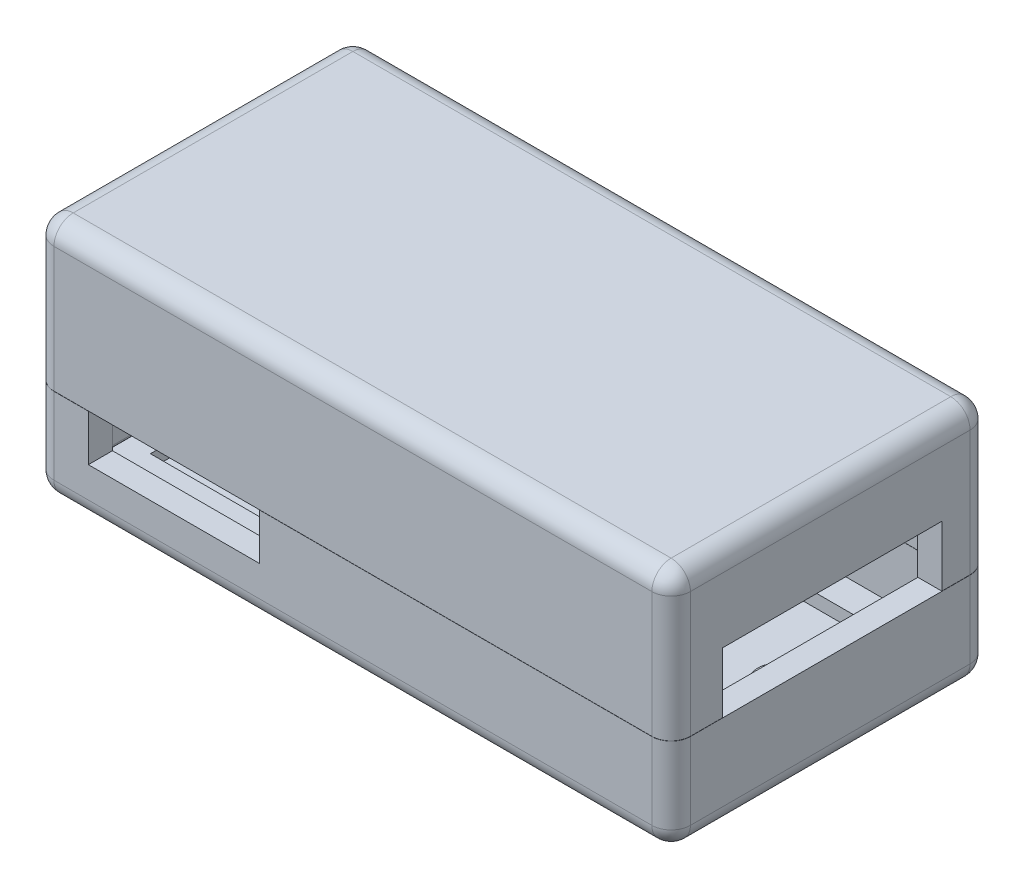
SolidWorks part; units mm, degrees
ref_plane "Front Plane" through (0, 0, 0) normal (0, 0, 1) x (1, 0, 0)
ref_plane "Top Plane" through (0, 0, 0) normal (0, 1, 0) x (1, 0, 0)
ref_plane "Right Plane" through (0, 0, 0) normal (1, 0, 0) x (0, 0, -1)
sketch "Sketch1" plane through (0, 0, 0) normal (0, 1, 0) x (1, 0, 0)
  line L1 (-41.91, -20.955) -> (41.91, -20.955)
  line L2 (-41.91, -20.955) -> (-41.91, 20.955)
  line L3 (-41.91, 20.955) -> (41.91, 20.955)
  line L4 (41.91, -20.955) -> (41.91, 20.955)
  line L5 (-41.91, -20.955) -> (41.91, 20.955) construction
  line L6 (-41.91, 20.955) -> (41.91, -20.955) construction
  point P0 (0, 0)
  dimension "D1" = 83.82
  dimension "D2" = 41.91
extrude "Boss-Extrude1" add sketch "Sketch1" along normal blind 31.75 contours L2 L3 L4 L1
sketch "Sketch2" plane through (0, 0, 20.955) normal (0, 0, 1) x (1, 0, 0)
  line L0 (-41.91, 31.75) -> (-41.91, 0) construction
  line L1 (-34.8361, 6.5761) -> (-12.2682, 6.5761)
  line L2 (-34.8361, 6.5761) -> (-34.8361, 12.6746)
  line L3 (-34.8361, 12.6746) -> (-12.2682, 12.6746)
  line L4 (-12.2682, 6.5761) -> (-12.2682, 12.6746)
  line L5 (-41.91, 0) -> (41.91, 0) construction
  dimension "D1" = 7.0739
  dimension "D2" = 29.6418
  dimension "D3" = 6.5761
  dimension "D4" = 12.6746
extrude "Cut-Extrude1" cut sketch "Sketch2" against normal through all
shell "Shell1" thickness 3.175 removed face at (-12.2682, 9.6253, 0) removed face at (-34.8361, 9.6253, 0) removed face at (-23.5522, 12.6746, 0) removed face at (-23.5522, 6.5761, 0)
sketch "Sketch4" plane through (-41.91, 0, 0) normal (-1, 0, 0) x (0, 0, 1)
  line L1 (-3.683, 6.5761) -> (3.683, 6.5761)
  line L2 (-3.683, 6.5761) -> (-3.683, 12.6746)
  line L3 (-3.683, 12.6746) -> (3.683, 12.6746)
  line L4 (3.683, 6.5761) -> (3.683, 12.6746)
  line L8 (-20.955, 31.75) -> (-20.955, 0) construction
  point P4 (0, 6.5761)
  dimension "D1" = 17.272
extrude "Cut-Extrude3" cut sketch "Sketch4" against normal up to next contours L2 L3 L4 L1
fillet "Fillet1" radius 2.54 12 edges at (-41.91, 15.875, 20.955) (41.91, 15.875, 20.955) (41.91, 15.875, -20.955) (-41.91, 15.875, -20.955) (41.91, 0, 0) (0, 0, -20.955) (-41.91, 0, 0) (0, 0, 20.955) (-41.91, 31.75, 0) (0, 31.75, -20.955) (41.91, 31.75, 0) (0, 31.75, 20.955)
sketch "Sketch5" plane through (0, 0, 20.955) normal (0, 0, 1) x (1, 0, 0)
  line L0 (-12.2682, 12.6746) -> (-34.8361, 12.6746) construction
  line L1 (-44.3024, 12.6746) -> (44.7358, 12.6746)
  line L2 (-44.3024, 12.6746) -> (-44.3024, 12.7)
  line L3 (-44.3024, 12.7) -> (44.7358, 12.7)
  line L4 (44.7358, 12.6746) -> (44.7358, 12.7)
  dimension "D1" = 0.0254
extrude "Cut-Extrude4" cut sketch "Sketch5" against normal through all
sketch "Sketch6" plane through (0, 3.175, 0) normal (0, 1, 0) x (1, 0, 0)
  line L0 (-38.735, 17.78) -> (38.735, 17.78)
  line L1 (38.735, 17.78) -> (38.735, -17.78)
  line L2 (38.735, -17.78) -> (-38.735, -17.78)
  line L3 (-38.735, -17.78) -> (-38.735, 17.78)
  line L4 (-33.655, -13.97) -> (-33.655, 13.97)
  line L5 (-33.655, 13.97) -> (34.925, 13.97)
  line L6 (34.925, 13.97) -> (34.925, 6.35)
  line L7 (34.925, -13.97) -> (-33.655, -13.97)
  line L8 (34.925, -6.35) -> (34.925, -13.97)
  line L9 (34.925, 6.35) -> (31.369, 6.35)
  line L11 (34.925, -6.35) -> (31.369, -6.35)
  line L12 (31.369, 6.35) -> (31.369, -6.35)
  point P16 (31.369, 0)
  point P19 (38.735, 0)
  dimension "D1" = 3.81
  dimension "D2" = 5.08
  dimension "D3" = 3.81
  dimension "D4" = 3.81
  dimension "D5" = 7.366
  dimension "D6" = 12.7
extrude "Boss-Extrude2" add sketch "Sketch6" along normal blind 1.7501
sketch "Sketch7" plane through (0, 4.9251, 0) normal (0, 1, 0) x (1, 0, 0)
  line L0 (31.369, -6.35) -> (31.369, 6.35) construction
  line L2 (38.735, -17.78) -> (38.735, 17.78) construction
  circle A0 centre (34.925, 0) radius 2.54
  circle A1 centre (34.925, 0) radius 0.635
  point P6 (31.369, 0)
  dimension "D1" = 5.08
  dimension "D3" = 1.27
  dimension "D2" = 3.81
extrude "Boss-Extrude3" add sketch "Sketch7" along normal blind 1.6002
sketch "Sketch8" plane through (-38.735, 0, 0) normal (1, 0, 0) x (0, 0, -1)
  line L0 (-17.78, 12.6746) -> (-17.78, 4.9251) construction
  line L1 (-17.78, 6.5761) -> (-3.683, 6.5761)
  line L2 (-17.78, 6.5761) -> (-17.78, 9.7511)
  line L3 (-17.78, 9.7511) -> (-3.683, 9.7511)
  line L4 (-3.683, 6.5761) -> (-3.683, 9.7511)
  line L5 (-3.683, 12.6746) -> (-3.683, 6.5761) construction
  line L6 (3.683, 12.6746) -> (3.683, 6.5761) construction
  line L7 (3.683, 9.7511) -> (17.78, 9.7511)
  line L8 (3.683, 9.7511) -> (3.683, 6.5761)
  line L9 (3.683, 6.5761) -> (17.78, 6.5761)
  line L10 (17.78, 9.7511) -> (17.78, 6.5761)
  line L11 (17.78, 12.6746) -> (17.78, 4.9251) construction
  line L12 (-3.683, 6.5761) -> (3.683, 6.5761) construction
  dimension "D1" = 3.175
extrude "Boss-Extrude4" add sketch "Sketch8" along normal blind 3.81
fillet "Fillet2" radius 0.508 2 edges at (-34.925, 6.5761, -10.7315) (-34.925, 6.5761, 10.7315)
sketch "Sketch9" plane through (41.91, 0, 0) normal (1, 0, 0) x (0, 0, -1)
  line L0 (-18.415, 12.7) -> (18.415, 12.7) construction
  line L1 (-14.175, 12.7) -> (14.6952, 12.7)
  line L2 (-14.175, 12.7) -> (-14.175, 20.6689)
  line L3 (-14.175, 20.6689) -> (14.6952, 20.6689)
  line L4 (14.6952, 12.7) -> (14.6952, 20.6689)
extrude "Cut-Extrude5" cut sketch "Sketch9" against normal up to next (3.175 mm away)
equation "\"wallThickness\"= 1 / 8in"
equation "\"D1@Sketch1\"=3.05in+2*\"wallThickness\""
equation "\"D2@Sketch1\"=1.4in+2*\"wallThickness\""
equation "\"D1@Sketch2\"=.1535+\"wallThickness\""
equation "\"D2@Sketch2\"=1.042+\"wallThickness\""
equation "\"D3@Sketch2\"=.1339+\"wallThickness\""
equation "\"D4@Sketch2\"=.374+\"wallThickness\""
equation "\"D1@Sketch4\"=0.555in+\"wallThickness\""
equation "\"D1@Shell1\"= \"wallThickness\""
equation "\"D1@Sketch8\"=\"wallThickness\""
